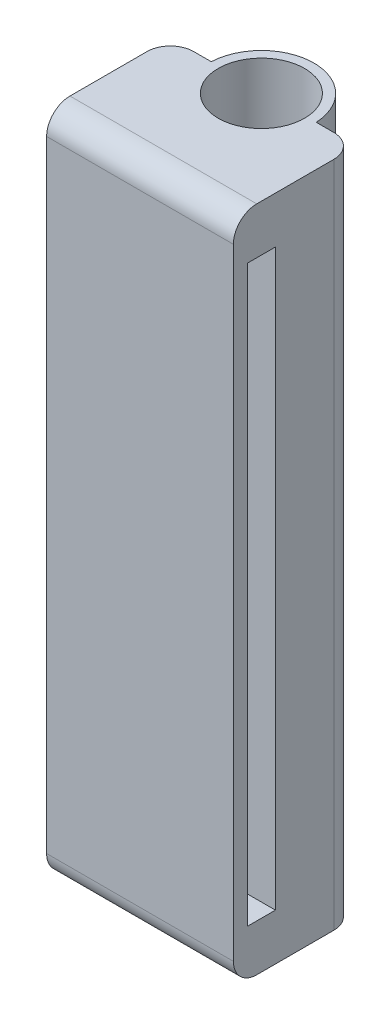
SolidWorks part; units mm, degrees
ref_plane "Front Plane" through (0, 0, 0) normal (0, 0, 1) x (1, 0, 0)
ref_plane "Top Plane" through (0, 0, 0) normal (0, 1, 0) x (1, 0, 0)
ref_plane "Right Plane" through (0, 0, 0) normal (1, 0, 0) x (0, 0, -1)
sketch "Sketch1" plane through (0, 0, 0) normal (0, 1, 0) x (1, 0, 0)
  line L0 (0, -26) -> (-20, -26)
  line L1 (0, -26) -> (20, -26)
  line L2 (-20, -26) -> (-20, -4.5)
  line L3 (-20, -4.5) -> (-20, -2.5)
  line L4 (-17, 0.5) -> (-11.2389, 0.5)
  line L5 (0, -26) -> (0, -20.3135) construction
  line L6 (17, 0.5) -> (11.2389, 0.5)
  line L7 (20, -4.5) -> (20, -2.5)
  line L8 (20, -26) -> (20, -4.5)
  line L9 (20, -2.5) -> (20, 0.5)
  line L10 (20, 0.5) -> (17, 0.5)
  line L11 (-17, 0.5) -> (-20, 0.5)
  line L12 (-20, 0.5) -> (-20, -2.5)
  circle A0 centre (0, 0) radius 9.25
  arc A1 (11.2389, 0.5) -> (-11.2389, 0.5) centre (0, 0) ccw
  point P12 (-20, 0.5)
  dimension "D1" = 18.5
  dimension "D4" = 2
  dimension "D2" = 26
  dimension "D3" = 20
  dimension "D5" = 21.5
  dimension "D6" = 5
extrude "Boss-Extrude1" add sketch "Sketch1" along normal blind 143
fillet "Fillet2" radius 5 2 edges at (-20, 71.5, -0.5) (20, 71.5, -0.5)
sketch "Sketch2" plane through (20, 0, 0) normal (1, 0, 0) x (0, 0, -1)
  line L0 (-26, 143) -> (-26, 0) construction
  line L1 (-23, 133) -> (-17, 133)
  line L2 (-23, 133) -> (-23, 10)
  line L3 (-23, 10) -> (-17, 10)
  line L4 (-17, 133) -> (-17, 10)
  line L5 (-26, 143) -> (-4.5, 143) construction
  line L6 (-26, 0) -> (-4.5, 0) construction
  dimension "D1" = 6
  dimension "D2" = 3
  dimension "D3" = 10
  dimension "D4" = 10
extrude "Cut-Extrude1" cut sketch "Sketch2" against normal offset from surface (37 mm away) 3 up to face at (-20, 71.5, 15.25)
fillet "Fillet3" radius 5 2 edges at (0, 0, 26) (0, 143, 26)
